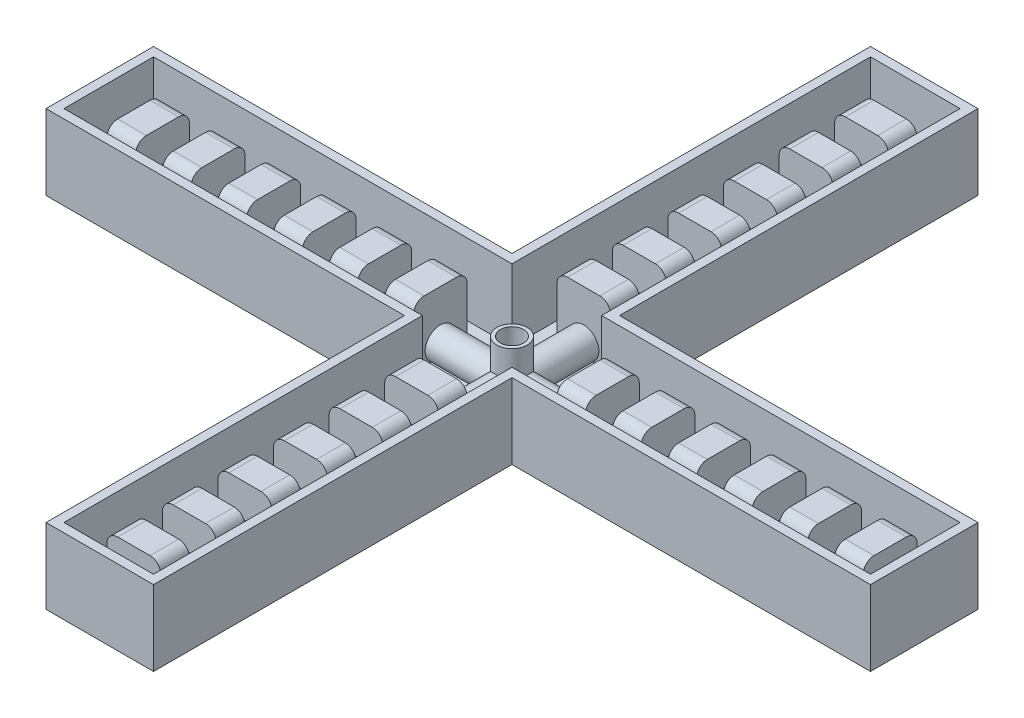
SolidWorks part; units mm, degrees
ref_plane "前视基准面" through (0, 0, 0) normal (0, 0, 1) x (1, 0, 0)
ref_plane "上视基准面" through (0, 0, 0) normal (0, 1, 0) x (1, 0, 0)
ref_plane "右视基准面" through (0, 0, 0) normal (1, 0, 0) x (0, 0, -1)
sketch "草图1" plane through (0, 0, 0) normal (0, 1, 0) x (1, 0, 0)
  line L1 (-15, -15) -> (15, -15)
  line L2 (-15, -15) -> (-15, 15)
  line L3 (-15, 15) -> (15, 15)
  line L4 (15, -15) -> (15, 15)
  line L5 (-15, -15) -> (15, 15) construction
  line L6 (-15, 15) -> (15, -15) construction
  line L7 (15, 15) -> (115, 15)
  line L9 (15, -15) -> (115, -15)
  line L10 (115, 15) -> (115, -15)
  point P0 (0, 0)
  dimension "D1" = 30
  dimension "D2" = 100
extrude "凸台-拉伸2" add sketch "草图1" along normal blind 1 contours L10 L7 L4 L9 region at (65, 0, 0)
sketch "草图2" plane through (0, 1, 0) normal (0, 1, 0) x (1, 0, 0)
  line L0 (15, -15) -> (15, 15) construction
  line L1 (12.49, 12.5) -> (112.5, 12.5)
  line L3 (12.49, -12.5) -> (112.5, -12.5)
  line L4 (112.5, 12.5) -> (112.5, -12.5)
  line L5 (15, 15) -> (115, 15) construction
  line L6 (15, -15) -> (115, -15) construction
  line L7 (115, 15) -> (115, -15) construction
  line L9 (12.49, -15) -> (115, -15)
  line L10 (115, 15) -> (115, -15)
  line L11 (12.49, 15) -> (115, 15)
  line L12 (12.49, -15) -> (12.49, 15)
  point P8 (0, 0)
  point P11 (0, 0)
  point P12 (0, 0)
  point P13 (13.9578, -12.5)
  point P14 (0, 0)
  line M5 (115, -15) -> (115, 15)
  line M6 (115, 15) -> (15, 15)
  line M7 (15, 15) -> (15, -15)
  line M8 (15, -15) -> (115, -15)
  dimension "D1" = 2.5
  dimension "D2" = 2.5
  dimension "D3" = 2.5
  dimension "D4" = 2.51
extrude "凸台-拉伸5" add sketch "草图2" along normal blind 20 contours L1 L4 L3 M7 M8 M5 M6 region at (16.044, 1, -13.75)
sketch "草图3" plane through (0, 1, 0) normal (0, 1, 0) x (1, 0, 0)
  line L1 (97.5, 7.5) -> (105.5, 7.5)
  line L2 (97.5, 7.5) -> (97.5, -7.5)
  line L3 (97.5, -7.5) -> (105.5, -7.5)
  line L4 (105.5, 7.5) -> (105.5, -7.5)
  line L20 (112.5, 12.5) -> (112.5, -12.5) construction
  line L21 (82, 7.5) -> (90, 7.5)
  line L22 (82, 7.5) -> (82, -7.5)
  line L23 (90, 7.5) -> (90, -7.5)
  line L24 (82, -7.5) -> (90, -7.5)
  line L25 (66.5, 7.5) -> (74.5, 7.5)
  line L26 (66.5, 7.5) -> (66.5, -7.5)
  line L27 (74.5, 7.5) -> (74.5, -7.5)
  line L28 (66.5, -7.5) -> (74.5, -7.5)
  line L29 (51, 7.5) -> (59, 7.5)
  line L30 (51, 7.5) -> (51, -7.5)
  line L31 (59, 7.5) -> (59, -7.5)
  line L32 (51, -7.5) -> (59, -7.5)
  line L33 (35.5, 7.5) -> (43.5, 7.5)
  line L34 (35.5, 7.5) -> (35.5, -7.5)
  line L35 (43.5, 7.5) -> (43.5, -7.5)
  line L36 (35.5, -7.5) -> (43.5, -7.5)
  line L37 (20, 7.5) -> (28, 7.5)
  line L38 (20, 7.5) -> (20, -7.5)
  line L39 (28, 7.5) -> (28, -7.5)
  line L40 (20, -7.5) -> (28, -7.5)
  point P22 (112.5, 0)
  point P23 (105.5, 0)
  dimension "D1" = 15
  dimension "D2" = 8
  dimension "D4" = 7
  dimension "D3" = 6
extrude "凸台-拉伸6" add sketch "草图3" along normal blind 17 contours L2 L1 L4 L3 | L21 L23 L24 L22 | L25 L27 L28 L26 | L29 L31 L32 L30 | L33 L35 L36 L34 | L37 L39 L40 L38
fillet "圆角1" radius 3 12 edges at (24, 18, 7.5) (39.5, 18, 7.5) (55, 18, 7.5) (70.5, 18, 7.5) (86, 18, 7.5) (101.5, 18, 7.5) (101.5, 18, -7.5) (86, 18, -7.5) (70.5, 18, -7.5) (55, 18, -7.5) (39.5, 18, -7.5) (24, 18, -7.5)
sketch "草图4" plane through (20, 0, 0) normal (-1, 0, 0) x (0, 0, 1)
  line L0 (-7.5, 1) -> (7.5, 1) construction
  line L1 (-7.5, 1) -> (7.5, 1)
  circle A0 centre (0, 4.5) radius 4.25
  point P4 (0, 0)
  point P5 (0, 1)
  dimension "D2" = 8.5
  dimension "D1" = 3.5
extrude "凸台-拉伸7" add sketch "草图4" against normal up to surface (85.5 mm away) contours L1 A0 region at (20, 4.6721, 0) up to face at (105.5, 11.5404, 0)
extrude "凸台-拉伸11" add sketch "草图1<4>" along normal blind 1 contours L1 L4 L3 L2 region at (0, 0, 0)
sketch "草图1<4>" plane through (0, 0, 0) normal (0, 1, 0) x (1, 0, 0) same geometry as "草图1"
sketch "草图7" plane through (0, 1, 0) normal (0, 1, 0) x (1, 0, 0)
  circle A0 centre (0, 0) radius 4.25
  circle A1 centre (0, 0) radius 3.25
  dimension "D1" = 8.5
  dimension "D2" = 6.5
extrude "凸台-拉伸12" add sketch "草图7" along normal blind 15
sketch "草图8" plane through (0, 16, 0) normal (0, 1, 0) x (1, 0, 0)
  circle A0 centre (0, 0) radius 3.25
sketch "草图9" plane through (0, 1, 0) normal (0, 1, 0) x (1, 0, 0)
  line L0 (15, -15) -> (15, -12.5) construction
  line L1 (15, 15) -> (12.5, 15)
  line L2 (15, 15) -> (15, 12.5)
  line L3 (15, 12.5) -> (12.5, 12.5)
  line L4 (12.5, 15) -> (12.5, 12.5)
  line L5 (15, -12.5) -> (12.5, -12.5)
  line L6 (15, -12.5) -> (15, -15)
  line L7 (15, -15) -> (12.5, -15)
  line L8 (12.5, -12.5) -> (12.5, -15)
  line L9 (-15, -15) -> (15, -15) construction
  dimension "D1" = 2.5
  dimension "D2" = 2.5
extrude "凸台-拉伸13" add sketch "草图9" along normal blind 20
pattern_circular "阵列(圆周)21" count 4 over 360 about axis through (0, 16, 0) along (0, -1, 0) of "凸台-拉伸2", "凸台-拉伸6", "圆角1"
pattern_circular "阵列(圆周)22" count 2 over 360 about axis through (0, 16, 0) along (0, -1, 0) of "凸台-拉伸5", "凸台-拉伸13"
extrude "凸台-拉伸14" add sketch "草图4<6>" along normal up to surface (125.5 mm away) contours L1 A0 region at (20, 4.6721, 0) up to face at (-105.5, 11.5404, 0)
sketch "草图4<6>" plane through (20, 0, 0) normal (-1, 0, 0) x (0, 0, 1) same geometry as "草图4"
sketch "草图11" plane through (0, 1, 0) normal (0, 1, 0) x (1, 0, 0)
  line L0 (12.5, 15) -> (12.5, 12.5) construction
  line L1 (12.5, 112.5) -> (-12.5, 112.5)
  line L2 (12.5, 112.5) -> (12.5, -112.5)
  line L3 (12.5, -112.5) -> (-12.5, -112.5)
  line L4 (-12.5, 112.5) -> (-12.5, -112.5)
  line L5 (-12.5, 12.5) -> (-12.5, 15) construction
  line L6 (-15, 115) -> (15, 115) construction
  line L7 (15, -115) -> (-15, -115) construction
  line L8 (-15, -15) -> (-12.5, -15) construction
  line L9 (12.5, -15) -> (15, -15) construction
  line L10 (-15, -115) -> (-15, -15) construction
  line L11 (15, -15) -> (15, -115) construction
  line L12 (15, 15) -> (12.5, 15) construction
  line L13 (-12.5, 15) -> (-15, 15) construction
  line L14 (15, 15) -> (15, 115) construction
  line L15 (-15, 15) -> (-15, 115) construction
  line L16 (-15, -15) -> (-12.5, -15)
  line L17 (12.5, -15) -> (15, -15)
  line L18 (15, -115) -> (-15, -115)
  line L19 (-15, -115) -> (-15, -15)
  line L20 (15, -15) -> (15, -115)
  line L21 (15, 15) -> (12.5, 15)
  line L22 (-12.5, 15) -> (-15, 15)
  line L23 (15, 15) -> (15, 115)
  line L24 (-15, 115) -> (15, 115)
  line L25 (-15, 15) -> (-15, 115)
  dimension "D1" = 2.5
  dimension "2.5" = 2.5
extrude "凸台-拉伸15" add sketch "草图11" along normal up to surface (20 mm away) contours L25 L22 L4 L1 L2 L21 L23 L24 | L20 L17 L2 L3 L4 L16 L19 L18 region at (0, 1, -113.544) region at (13.75, 1, 16.044)
sketch "草图12" plane through (0, 0, -20) normal (0, 0, 1) x (1, 0, 0)
  line L0 (-7.5, 1) -> (7.5, 1) construction
  line L1 (7.5, 15) -> (7.5, 1) construction
  line L2 (-7.5, 15) -> (-7.5, 1) construction
  line L3 (-7.5, 1) -> (7.5, 1)
  circle A0 centre (0, 4.5) radius 4.25
  point P4 (0, 0)
  point P5 (0, 0)
  point P6 (0, 0)
  dimension "D1" = 8.5
  dimension "D2" = 3.5
  dimension "D3" = 7.5
  dimension "D4" = 7.5
extrude "凸台-拉伸16" add sketch "草图12" along normal up to surface and the other way up to surface contours L3 A0 region at (0, 4.6721, -20) up to face at (0, 11.5404, 105.5) other way up to face at (0, 11.5404, -105.5)
extrude "切除-拉伸4" cut sketch "草图8" against normal blind 15
